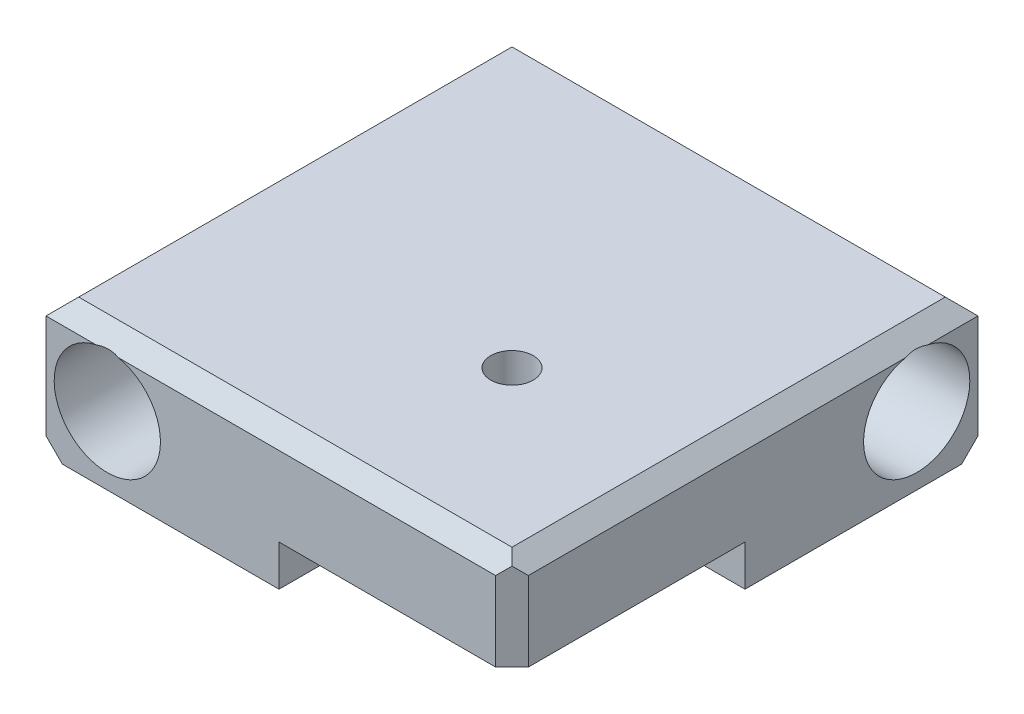
SolidWorks part; units mm, degrees
ref_plane "Front Plane" through (0, 0, 0) normal (0, 0, 1) x (1, 0, 0)
ref_plane "Top Plane" through (0, 0, 0) normal (0, 1, 0) x (1, 0, 0)
ref_plane "Right Plane" through (0, 0, 0) normal (1, 0, 0) x (0, 0, -1)
sketch "Sketch1" plane through (0, 0, 0) normal (0, 1, 0) x (1, 0, 0)
  line L1 (7.5, -5) -> (-7.5, -5)
  line L2 (7.5, -5) -> (7.5, 5)
  line L3 (7.5, 5) -> (-7.5, 5)
  line L4 (-7.5, -5) -> (-7.5, 5)
  line L5 (7.5, -5) -> (-7.5, 5) construction
  line L6 (7.5, 5) -> (-7.5, -5) construction
  line L8 (-7.5, 5) -> (-7.5, 20)
  line L9 (-7.5, 20) -> (7.5, 20)
  line L10 (7.5, 5) -> (7.5, 20)
  line L11 (7.5, 5) -> (17.5, 5)
  line L13 (7.5, 20) -> (17.5, 20)
  line L14 (17.5, 5) -> (17.5, 20)
  point P0 (0, 0)
  dimension "D1" = 10
  dimension "D2" = 15
  dimension "D3" = 15
  dimension "D4" = 10
extrude "Boss-Extrude1" add sketch "Sketch1" along normal blind 16.7 contours L4 L1 L2 L3 | L3 L10 L9 L8 | L11 L14 L13 L10
sketch "Sketch2" plane through (0, 0, 5) normal (0, 0, 1) x (1, 0, 0)
  line L0 (0, 0) -> (0, 16.7) construction
  line L1 (7.5, 0) -> (-7.5, 0) construction
  line L2 (7.5, 16.7) -> (-7.5, 16.7) construction
  circle A0 centre (0, 8.35) radius 6.5
  dimension "D1" = 13
extrude "Cut-Extrude1" cut sketch "Sketch2" against normal offset from surface (8.3 mm away) 16.7 up to face at (5, 8.35, -20)
sketch "Sketch3" plane through (17.5, 0, 0) normal (1, 0, 0) x (0, 0, -1)
  line L0 (12.5, 0) -> (12.5, 16.7) construction
  line L1 (5, 0) -> (20, 0) construction
  line L2 (5, 16.7) -> (20, 16.7) construction
  circle A0 centre (12.5, 8.35) radius 6.5
  dimension "D1" = 13
extrude "Cut-Extrude2" cut sketch "Sketch3" against normal offset from surface (8.3 mm away) 16.7 up to face at (-7.5, 8.35, -7.5)
sketch "Sketch4" plane through (0, 0, 0) normal (0, -1, 0) x (1, 0, 0)
  line L0 (0, 5) -> (0, -20) construction
  line L1 (7.5, 5) -> (-7.5, 5) construction
  line L2 (-7.5, -20) -> (17.5, -20) construction
  line L3 (17.5, -12.5) -> (-7.5, -12.5) construction
  line L4 (17.5, -5) -> (17.5, -20) construction
  line L5 (-7.5, 5) -> (-7.5, -20) construction
  circle A0 centre (0, -12.5) radius 6.5
  dimension "D1" = 13
extrude "Cut-Extrude3" cut sketch "Sketch4" against normal offset from surface (14.7 mm away) 2 up to face at (5.8333, 16.7, -6.6667)
fillet "Fillet8" radius 2 5 edges at (-7.5, 8.35, -20) (-7.5, 0, -7.5) (-7.5, 16.7, -7.5) (5, 16.7, -20) (5, 0, -20) profile chamfer
sketch "Sketch5" plane through (0, 16.7, 0) normal (0, 1, 0) x (1, 0, 0)
  line L1 (7.5, -37) -> (49.5, -37)
  line L2 (7.5, -37) -> (7.5, 5)
  line L3 (7.5, 5) -> (49.5, 5)
  line L4 (49.5, -37) -> (49.5, 5)
  line L6 (7.5, -16) -> (49.5, -16) construction
  line L7 (28.5, 5) -> (28.5, -37) construction
  line L8 (29.5, -17) -> (27.5, -17)
  line L9 (29.5, -17) -> (29.5, -15)
  circle A4 centre (28.5, -16) radius 2.6
  point P14 (28.5, 0)
  point P15 (12.5, -16)
  point P17 (28.5, -17)
  point P18 (29.5, -16)
  dimension "D8" = 5.2
  dimension "D1" = 42
  dimension "D2" = 42
extrude "Boss-Extrude3" add sketch "Sketch5" against normal up to surface (16.7 mm away) up to face at (6.8683, 0, -5.6317)
fillet "Fillet9" radius 2 1 edges at (49.5, 8.35, 37) profile chamfer
sketch "Sketch7" plane through (0, 0, 5) normal (0, 0, 1) x (1, 0, 0)
  line L0 (-5.5, 16.7) -> (-7.5, 14.7)
  line L1 (-5.5, 16.7) -> (-7.5, 14.7) construction
  line L2 (-7.5, 14.7) -> (-7.5, 2)
  line L3 (-7.5, 2) -> (-5.5, 0)
  line L4 (-5.5, 0) -> (7.5, 0)
  line L5 (7.5, 0) -> (7.5, 16.7)
  line L6 (7.5, 16.7) -> (-5.5, 16.7)
  circle A0 centre (0, 8.35) radius 6.5
extrude "Boss-Extrude4" add sketch "Sketch7" along normal up to surface (32 mm away) up to face at (27.5, 8.35, 37)
sketch "Sketch8" plane through (17.5, 0, 0) normal (1, 0, 0) x (0, 0, -1)
  line L0 (5, 16.7) -> (5, 0)
  line L1 (5, 0) -> (18, 0)
  line L2 (18, 0) -> (20, 2)
  line L3 (20, 2) -> (20, 14.7)
  line L4 (20, 14.7) -> (18, 16.7)
  line L5 (18, 16.7) -> (5, 16.7)
  circle A0 centre (12.5, 8.35) radius 6.5
extrude "Boss-Extrude5" add sketch "Sketch8" along normal up to surface (32 mm away) up to face at (49.5, 8.35, 15)
sketch "Sketch9" plane through (0, 0, 0) normal (0, -1, 0) x (1, 0, 0)
  line L0 (28.5, 8.5) -> (49.5, 8.5)
  line L1 (49.5, -18) -> (49.5, 35) construction
  line L2 (49.5, 8.5) -> (49.5, 35)
  line L3 (49.5, 35) -> (47.5, 37)
  line L4 (47.5, 37) -> (28.5, 37)
  line L5 (47.5, 37) -> (-5.5, 37) construction
  line L6 (28.5, 37) -> (21, 37)
  line L7 (21, 37) -> (21, 16)
  arc A0 (21, 16) -> (28.5, 8.5) centre (28.5, 16) ccw
  dimension "D1" = 15
extrude "Cut-Extrude4" cut sketch "Sketch9" against normal blind 5
chamfer "Chamfer1" distance 2 angle 45 2 edges at (49.5, 16.7, 8.5) (21, 16.7, 37)
